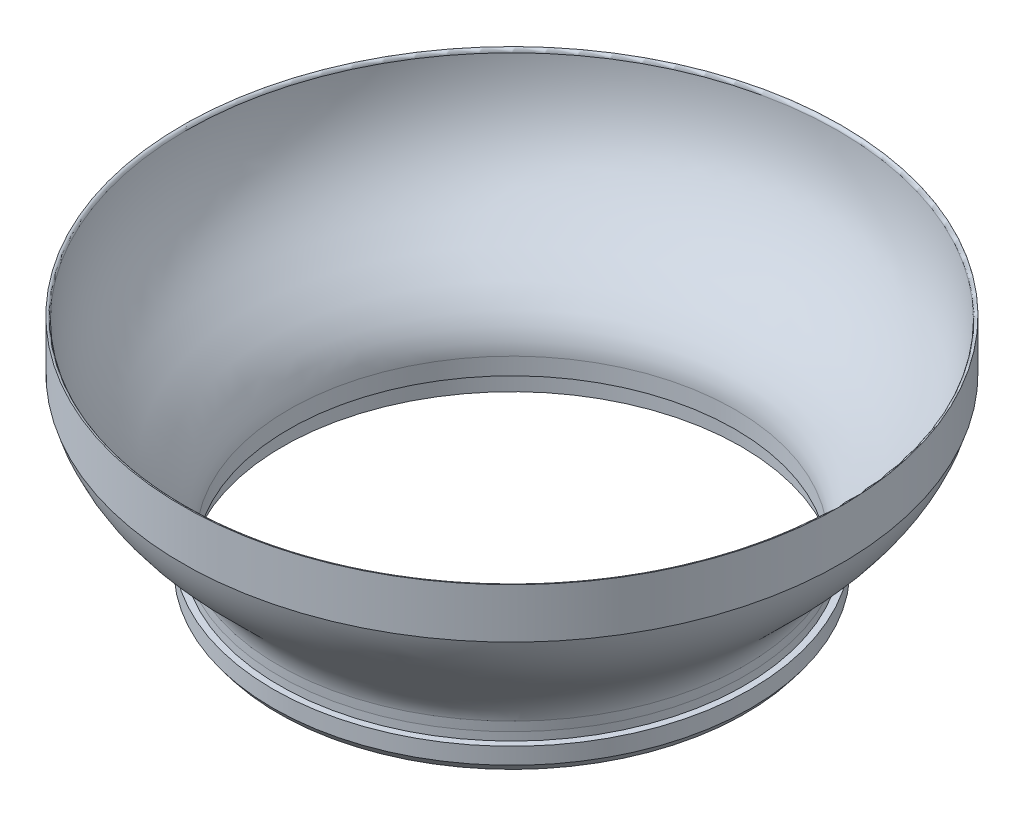
SolidWorks part; units mm, degrees
ref_plane "Front Plane" through (0, 0, 0) normal (0, 0, 1) x (1, 0, 0)
ref_plane "Top Plane" through (0, 0, 0) normal (0, 1, 0) x (1, 0, 0)
ref_plane "Right Plane" through (0, 0, 0) normal (1, 0, 0) x (0, 0, -1)
sketch "Sketch1" plane through (0, 0, 0) normal (0, 0, 1) x (1, 0, 0)
  line L0 (0, 0) -> (30.4865, 0) construction
  line L1 (0, 0) -> (0, 36.8) construction
  line L2 (0, 0) -> (-52, 0) construction
  line L3 (-52, 0) -> (-52, 33.8662) construction
  line L4 (-36.8, 0) -> (-36.2, 0)
  line L5 (-36.2, 0) -> (-36.2, 2.3)
  line L6 (-36.2, 2.3) -> (-35.2, 2.3)
  line L7 (-35.2, 2.3) -> (-35.2, 5.5667)
  line L8 (-35.2, 5.5667) -> (-52.5105, 29.6401) construction
  line L9 (-36.7, 5.0834) -> (-53.7283, 28.7644) construction
  line L10 (-37.7, 1.2) -> (-37.7, 1.2)
  line L11 (-37.7, 1.2) -> (-37.7, 3.8)
  line L12 (-37.7, 3.8) -> (-36.7, 3.8)
  line L13 (-36.7, 3.8) -> (-36.7, 5.0834)
  line L14 (-36.8, 0) -> (-37.7, 1.2)
  line L15 (-51.5, 0) -> (-51.5, 35.9874) construction
  line L16 (-43.7, 63.2571) -> (-43.7, -12.721) construction
  line L17 (-52, 0) -> (-52, 28.4324) construction
  line L18 (-51.5, 0) -> (-51.5, 28.4324) construction
  line L19 (-51.5, 43.1556) -> (-51.5, 28.8191) construction
  line L20 (-35.2, 9.5413) -> (-35.2, 1.5921) construction
  line L21 (-36.7, 5.0834) -> (-36.7851, 6.581)
  line L31 (-52, 28.1375) -> (-52, 35.9874)
  line L32 (-52, 35.9874) -> (-51.5, 35.9874)
  line L34 (-36.7851, 6.581) -> (-36.7851, 6.581) construction
  line L35 (-36.7851, 6.581) -> (-36.7851, 6.581) construction
  line L36 (-36.7851, 6.581) -> (-36.7851, 6.581) construction
  line L37 (-36.7851, 6.581) -> (-36.7851, 6.581) construction
  line L38 (-36.7851, 6.581) -> (-36.7851, 6.581) construction
  line L39 (-36.7851, 6.581) -> (-36.7851, 6.581) construction
  line L40 (-36.7851, 6.581) -> (-36.7851, 6.581) construction
  line L41 (-36.7851, 6.581) -> (-36.7851, 6.581) construction
  line L42 (-36.7851, 6.581) -> (-36.7851, 6.581) construction
  spline S0 degree 3 poles (-35.2, 5.5667) (-35.2, 10.0381) (-40.1574, 14.4015) (-48.377, 22.5683) (-51.5, 27.9231) (-51.5, 35.9874) knots 0 0 0 0 0.399182 0.499182 1 1 1 1
  spline S1 degree 1 poles (-36.7851, 6.581) (-53, 35.9874) knots 0 0 1 1 construction
  spline S2 degree 3 poles (-36.7851, 6.581) (-36.8743, 7.1122) (-37.179, 8.1272) (-38.281, 10.1908) (-40.4475, 12.7421) (-43.6502, 15.7487) (-46.6708, 18.7629) (-49.2926, 22.0197) (-51.0162, 25.1773) (-52.0252, 28.0742) (-52.5807, 30.4525) (-52.8651, 32.6333) (-52.9805, 34.4966) (-53, 35.496) (-53, 35.9874) knots 0.038363 0.038363 0.038363 0.038363 0.098465 0.158568 0.278772 0.398977 0.519181 0.639386 0.759591 0.819693 0.879795 0.939898 0.969949 1 1 1 1 only from (-36.7851, 6.581) to (-52, 28.1375)
  dimension "D1" = 0.5
  dimension "D2" = 0.6
  dimension "D3" = 1.6
  dimension "D4" = 52
  dimension "D5" = 1.5
  dimension "D6" = 36.8
  dimension "D7" = 2.3
  dimension "D8" = 7
  dimension "D9" = 35.9874
  dimension "D10" = 1.5
revolve "Revolve1" add sketch "Sketch1" angle 360 about L1
fillet "Fillet1" radius 0.5 1 edges at (0, 35.9874, -51.5)
chamfer "Chamfer1" distance 1 angle 30 1 edges at (0, 2.3, -35.2) first distance on face at (0, 2.3, -35.2)
